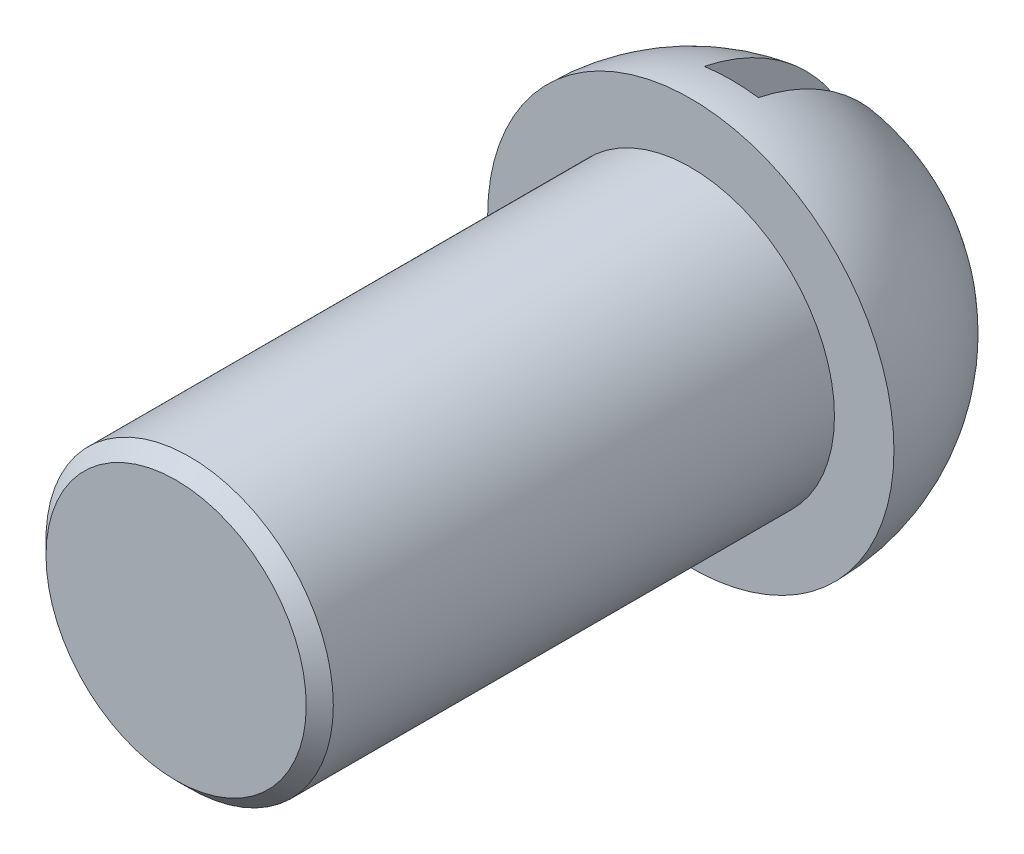
SolidWorks part; units mm, degrees
ref_plane "Front Plane" through (0, 0, 0) normal (0, 0, 1) x (1, 0, 0)
ref_plane "Top Plane" through (0, 0, 0) normal (0, 1, 0) x (1, 0, 0)
ref_plane "Right Plane" through (0, 0, 0) normal (1, 0, 0) x (0, 0, -1)
sketch "Sketch1" plane through (0, 0, 0) normal (0, 1, 0) x (1, 0, 0)
  line L0 (0, 0) -> (0, 38)
  line L1 (10.6066, 38) -> (15, 38)
  line L2 (0, 38) -> (0, 53)
  line L3 (0, 0) -> (10.6066, 0)
  line L4 (10.6066, 38) -> (10.6066, 0)
  arc A0 (0, 53) -> (15, 38) centre (0, 38) cw
revolve "Revolve1" add sketch "Sketch1" angle 360 about L0
sketch "Sketch3" plane through (0, 0, 0) normal (0, 1, 0) x (1, 0, 0)
  line L0 (-2.0024, 52.8669) -> (1.9935, 52.8669)
  line L1 (-2.0024, 52.8669) -> (-2.0024, 41)
  line L4 (1.9935, 41) -> (1.9935, 52.8669)
  line L6 (-2.0024, 41) -> (1.9935, 41)
  arc A0 (15, 38) -> (-15, 38) centre (0, 38) ccw construction
  point P6 (-0.0044, 52.8669)
extrude "Cut-Extrude2" cut sketch "Sketch3" against normal blind 17 and the other way blind 17
sketch "Sketch4" plane through (0, 0, -52.8669) normal (0, 0, 1) x (1, 0, 0)
  circle A0 centre (0, 0) radius 1.9935
extrude "Cut-Extrude3" cut sketch "Sketch4" against normal blind 5
chamfer "Chamfer1" distance 1 angle 45 1 edges at (10.6066, 0, 0)
